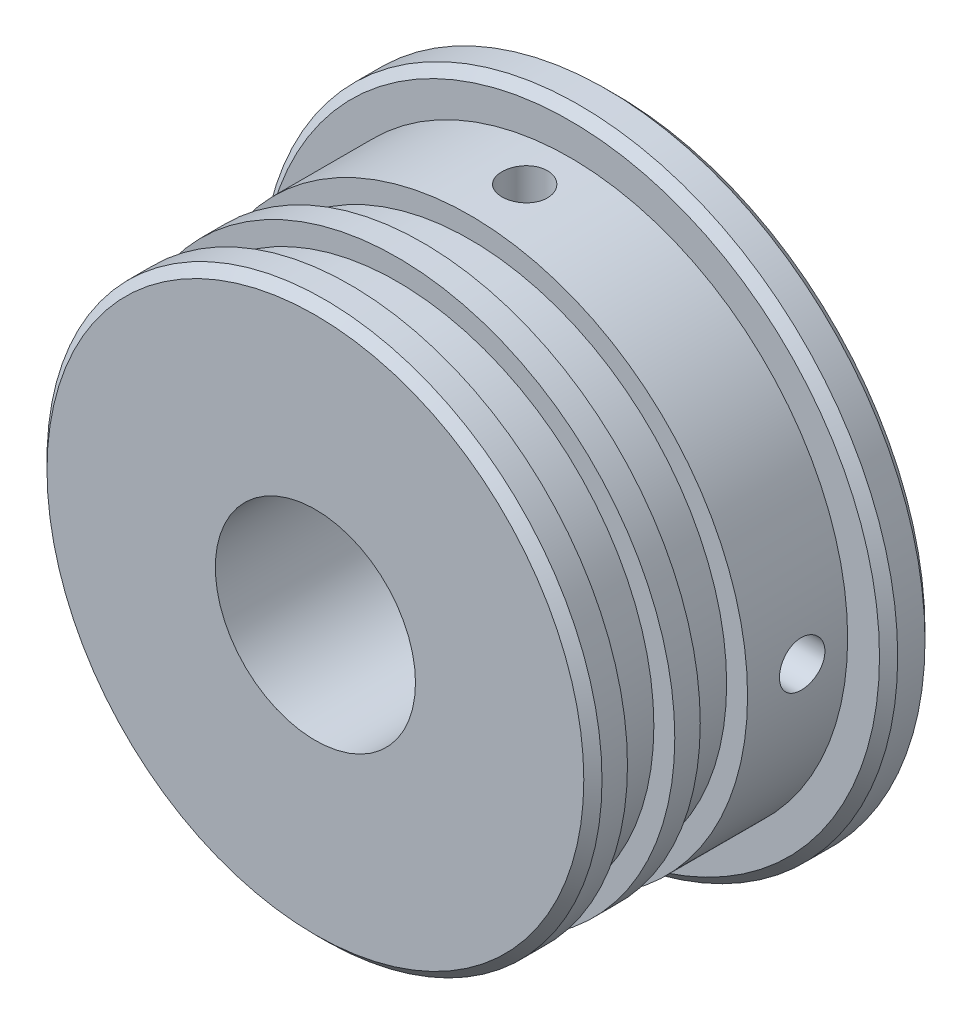
SolidWorks part; units mm, degrees
ref_plane "Спереди" through (0, 0, 0) normal (0, 0, 1) x (1, 0, 0)
ref_plane "Сверху" through (0, 0, 0) normal (0, 1, 0) x (1, 0, 0)
ref_plane "Справа" through (0, 0, 0) normal (1, 0, 0) x (0, 0, -1)
other "Configuration Table"
sketch "Эскиз1" plane through (0, 0, 0) normal (0, 0, 1) x (1, 0, 0)
  circle A0 centre (0, 0) radius 17.5
  circle A1 centre (0, 0) radius 15.25
  circle A2 centre (0, 0) radius 14.1
  circle A3 centre (0, 0) radius 5.5
  dimension "D1" = 35
  dimension "D2" = 30.5
  dimension "D3" = 28.2
  dimension "D4" = 11
extrude "Бобышка-Вытянуть1" add sketch "Эскиз1" against normal blind 2.5 contours A0 A1 | A1 A2 | A2 region at (-17.005, 0, 0) region at (-14.8187, 0, 0) region at (-13.7012, 0, 0)
extrude "Бобышка-Вытянуть2" add sketch "Эскиз1<3>" along normal blind 14 contours A1 A2 | A2 region at (-14.8187, 0, 0) region at (-13.7012, 0, 0)
sketch "Эскиз1<3>" plane through (0, 0, 0) normal (0, 0, 1) x (1, 0, 0) same geometry as "Эскиз1"
extrude "Вырез-Вытянуть1" cut sketch "Эскиз1<4>" along normal blind 2.6 from offset 5.5 contours A1 A2 region at (-14.8187, 0, 0)
sketch "Эскиз1<4>" plane through (0, 0, 0) normal (0, 0, 1) x (1, 0, 0) same geometry as "Эскиз1"
extrude "Вырез-Вытянуть2" cut sketch "Эскиз1<5>" along normal blind 2.6 from offset 9.5 contours A1 A2 region at (-14.8187, 0, 0)
sketch "Эскиз1<5>" plane through (0, 0, 0) normal (0, 0, 1) x (1, 0, 0) same geometry as "Эскиз1"
chamfer "Фаска1" distance 0.5 angle 45 3 edges at (15.25, 0, 14) (17.5, 0, 0) (17.5, 0, -2.5)
sketch "Эскиз2" plane through (0, 0, -2.5) normal (0, 0, -1) x (-1, 0, 0)
  circle A0 centre (0, 0) radius 6
  dimension "D1" = 12
extrude "Вырез-Вытянуть3" cut sketch "Эскиз2" against normal blind 2.5
sketch "Эскиз3" plane through (0, 0, 0) normal (0, 1, 0) x (1, 0, 0)
  line L0 (0, 0) -> (0, 5.0181)
  circle A0 centre (0, -2.5) radius 1.25
  dimension "D1" = 2.5
  dimension "D2" = 2.5
extrude "Вырез-Вытянуть4" cut sketch "Эскиз3" along normal blind 10 from offset 10 contours A0 region at (0, 0, 2.5)
pattern_circular "Круговой массив1" count 4 every 90 about axis through (0, 0, 0) along (0, 0, -1) of "Вырез-Вытянуть4"
